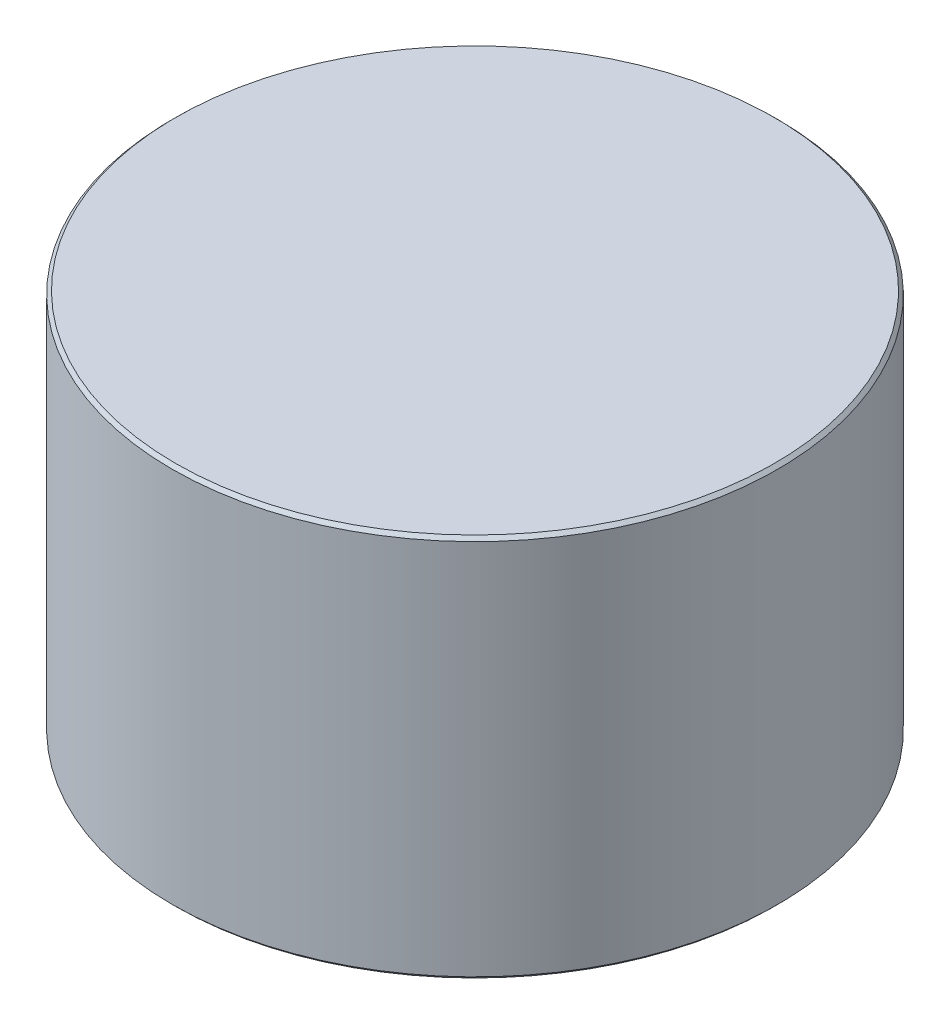
SolidWorks part; units mm, degrees
material "6061 Alloy"
ref_plane "Front Plane" through (0, 0, 0) normal (0, 0, 1) x (1, 0, 0)
ref_plane "Top Plane" through (0, 0, 0) normal (0, 1, 0) x (1, 0, 0)
ref_plane "Right Plane" through (0, 0, 0) normal (1, 0, 0) x (0, 0, -1)
sketch "main_dimensions_sketch" plane through (0, 0, 0) normal (0, 1, 0) x (1, 0, 0)
  circle A0 centre (0, 0) radius 5.5
  circle A1 centre (0, 0) radius 9
  dimension "D1" = 11
  dimension "D2" = 18
extrude "body" add sketch "main_dimensions_sketch" along normal blind 10 contours A1
extrude "lip" add sketch "Sketch1<3>" against normal blind 1.4 contours A1 A0 region at (-8.7454, 0, 0)
sketch "Sketch1<3>" plane through (0, 0, 0) normal (0, 1, 0) x (1, 0, 0) same geometry as "main_dimensions_sketch"
chamfer "break_edges" distance 0.1 angle 45 3 edges at (0, -1.4, 9) (0, -1.4, 5.5) (0, 10, 9)
